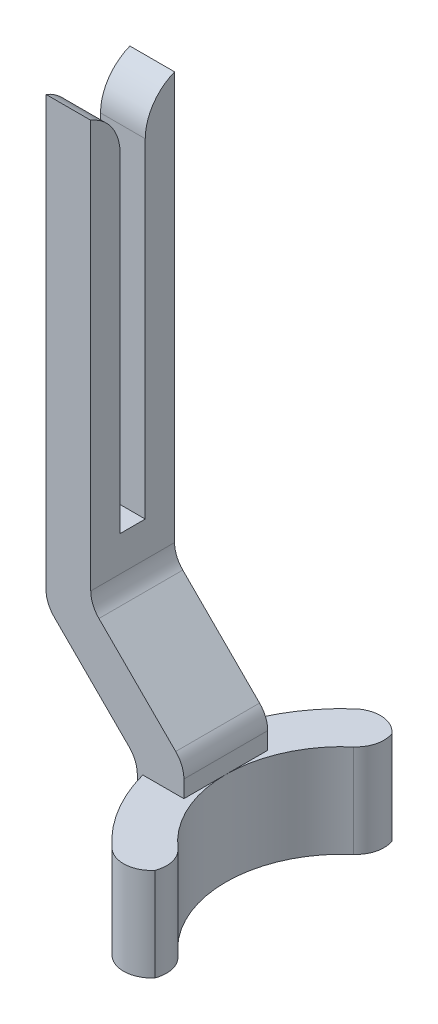
SolidWorks part; units mm, degrees
ref_plane "Front Plane" through (0, 0, 0) normal (0, 0, 1) x (1, 0, 0)
ref_plane "Top Plane" through (0, 0, 0) normal (0, 1, 0) x (1, 0, 0)
ref_plane "Right Plane" through (0, 0, 0) normal (1, 0, 0) x (0, 0, -1)
sketch "Sketch1" plane through (0, 0, 0) normal (0, 1, 0) x (1, 0, 0)
  line L0 (0, 4.5) -> (4.8, 4.5) construction
  line L1 (0, 0) -> (4.8, 0)
  line L2 (0, 0) -> (0, 9)
  line L3 (0, 9) -> (4.8, 9)
  line L4 (4.8, 0) -> (4.8, 9)
  line L6 (4.8, 3.15) -> (0, 3.15)
  line L7 (4.8, 3.15) -> (4.8, 5.85)
  line L8 (4.8, 5.85) -> (0, 5.85)
  line L9 (0, 3.15) -> (0, 5.85)
  line L10 (4.8, 3.15) -> (0, 5.85) construction
  line L11 (4.8, 5.85) -> (0, 3.15) construction
  point P7 (2.4, 4.5)
  dimension "D1" = 2.7
  dimension "D2" = 4.8
  dimension "D3" = 9
extrude "Boss-Extrude1" add sketch "Sketch1" along normal blind 40 contours L8 L4 L3 L2 | L4 L6 L2 L1
sketch "Sketch2" plane through (0, 0, 0) normal (0, -1, 0) x (1, 0, 0)
  line L1 (0, 0) -> (4.8, 0)
  line L2 (0, 0) -> (0, -9)
  line L3 (0, -9) -> (4.8, -9)
  line L4 (4.8, 0) -> (4.8, -9)
extrude "Boss-Extrude2" add sketch "Sketch2" along normal blind 5
sketch "Sketch3" plane through (4, 0, 0) normal (0, 0, -1) x (-1, 0, 0)
  line L0 (4, -7.2711) -> (-5.8, -17.0711)
  line L1 (-0.8, -5) -> (-5.8, -10)
  line L2 (-5.8, -10) -> (-5.8, -17.0711)
  line L3 (-5.8, -10) -> (-10.8, -15)
  line L4 (-10.8, -15) -> (-10.8, -18.0711)
  line L5 (-10.8, -18.0711) -> (-5.8, -18.0711)
  line L6 (-5.8, -18.0711) -> (-5.8, -17.0711)
  line L7 (-10.8, -15) -> (-10.8, -5) construction
  line L8 (-10.8, -5) -> (-0.8, -5) construction
  line L9 (4, -5) -> (4, -7.2711)
  dimension "D1" = 5
  dimension "D2" = 1
  dimension "D3" = 10
  dimension "D4" = 5
extrude "Boss-Extrude3" add sketch "Sketch3" along normal up to surface (9 mm away) up to face at (2.4, 17.5, -9)
sketch "Sketch4" plane through (0, -18.0711, 0) normal (0, -1, 0) x (1, 0, 0)
  line L1 (27.3, -4.5) -> (9.8, -4.5) construction
  line L3 (9.8, 0) -> (10.3885, 0)
  line L5 (14.8, 0) -> (9.8, 0) construction
  line L6 (9.8, -9) -> (9.8, 0)
  line L7 (27.3, -4.5) -> (18.55, -19.6554)
  line L8 (27.3, -4.5) -> (18.55, 10.6554)
  line L9 (14.8, 0) -> (14.8, -9)
  circle A2 centre (27.3, -4.5) radius 17.5
  circle A3 centre (27.3, -4.5) radius 12.5
  arc A4 (22.925, -12.0777) -> (22.925, 3.0777) centre (27.3, -4.5) cw
  point P5 (9.8, -4.5)
  point P20 (18.55, -4.5)
  line M9 (9.8, -9) -> (14.8, -9)
  line M10 (14.8, -9) -> (14.8, 0)
  line M11 (14.8, 0) -> (9.8, 0)
  line M12 (9.8, 0) -> (9.8, -9)
  dimension "D3" = 120
  dimension "D1" = 5
  dimension "D2" = 25
extrude "Boss-Extrude4" add sketch "Sketch4" along normal blind 10 contours A2 M11 M12 | A2 L6 M9 | A3 A2 L7 M10 M9 | L1 A2 M10 M9 | L1 L9 A2 M11 | A3 L8 A2 L9 M11
fillet "Fillet1" radius 5 2 edges at (2.4, 40, -3.15) (2.4, 40, -5.85)
fillet "Fillet2" radius 3 4 edges at (21.05, -23.0711, 6.3253) (21.05, -23.0711, -15.3253) (18.55, -23.0711, -19.6554) (18.55, -23.0711, 10.6554)
fillet "Fillet3" radius 3 4 edges at (0, -7.2711, -4.5) (4.8, -5, -4.5) (14.8, -15, -4.5) (9.8, -17.0711, -4.5)
